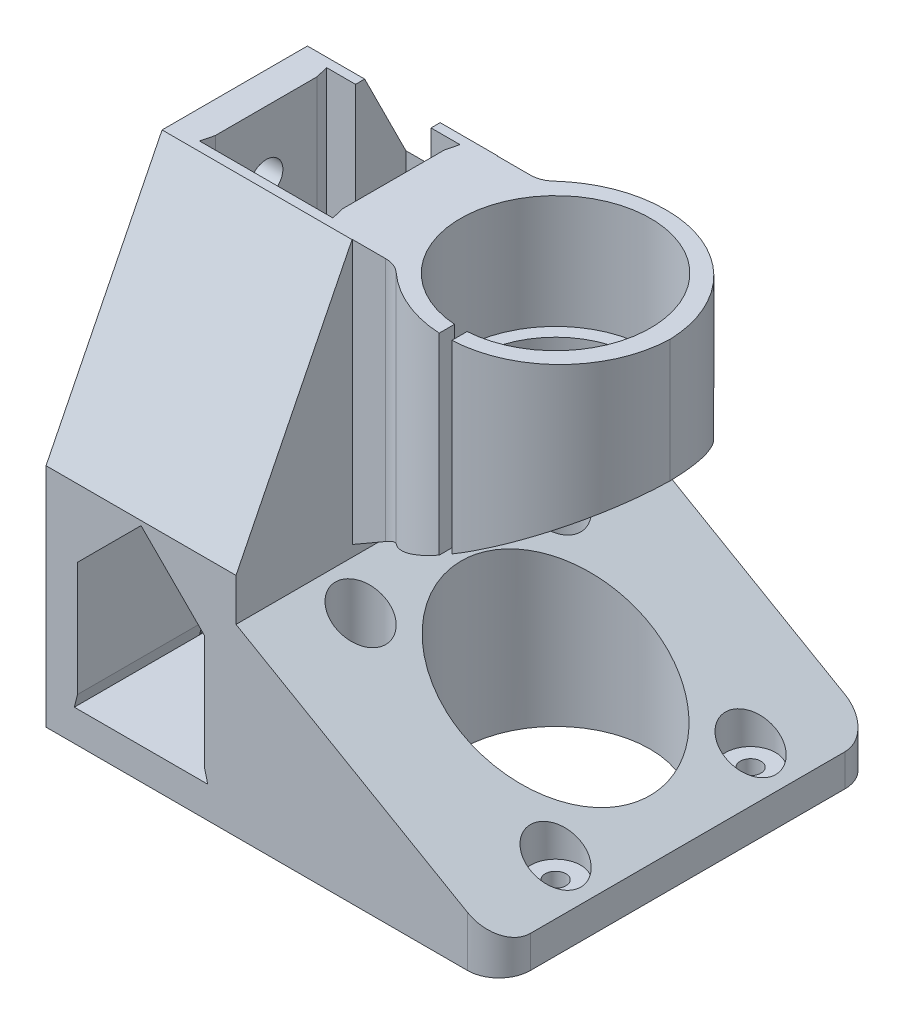
SolidWorks part; units mm, degrees
ref_plane "Front Plane" through (0, 0, 0) normal (0, 0, 1) x (1, 0, 0)
ref_plane "Top Plane" through (0, 0, 0) normal (0, 1, 0) x (1, 0, 0)
ref_plane "Right Plane" through (0, 0, 0) normal (1, 0, 0) x (0, 0, -1)
sketch "Sketch1" plane through (0, 0, 0) normal (0, 1, 0) x (1, 0, 0)
  line L1 (0, 0) -> (72, 0)
  line L2 (0, 0) -> (0, 60)
  line L3 (0, 60) -> (72, 60)
  line L4 (72, 0) -> (72, 60)
  dimension "D1" = 72
  dimension "D2" = 60
extrude "Boss-Extrude1" add sketch "Sketch1" along normal blind 5
sketch "Sketch2" plane through (0, 5, 0) normal (0, 1, 0) x (1, 0, 0)
  line L0 (0, 0) -> (72, 0) construction
  line L1 (0, 60) -> (5, 60)
  line L2 (0, 60) -> (0, 0)
  line L3 (0, 0) -> (5, 0)
  line L4 (5, 60) -> (5, 0)
  dimension "D1" = 5
extrude "Boss-Extrude2" add sketch "Sketch2" along normal blind 68
sketch "Sketch3" plane through (0, 5, 0) normal (0, 1, 0) x (1, 0, 0)
  line L0 (72, 60) -> (5, 60) construction
  line L1 (25.2, 60) -> (30.2, 60)
  line L2 (25.2, 60) -> (25.2, 0)
  line L3 (25.2, 0) -> (30.2, 0)
  line L4 (30.2, 60) -> (30.2, 0)
  line L5 (5, 0) -> (72, 0) construction
  line L6 (5, 0) -> (5, 60) construction
  dimension "D1" = 5
  dimension "D2" = 20.2
extrude "Boss-Extrude3" add sketch "Sketch3" along normal blind 68
sketch "Sketch11" plane through (0, 0, -60) normal (0, 0, -1) x (-1, 0, 0)
  line L0 (-25.2, 25.2) -> (-15.1, 35.3)
  line L1 (-25.2, 73) -> (-25.2, 5) construction
  line L2 (-15.1, 35.3) -> (-5, 25.2)
  line L3 (-5, 73) -> (-5, 5) construction
  line L4 (-5, 25.2) -> (-5, 73)
  line L5 (-5, 73) -> (-25.2, 73)
  line L6 (-25.2, 73) -> (-25.2, 25.2)
  line L7 (-25.2, 5) -> (-5, 5) construction
  dimension "D1" = 20.2
  dimension "D2" = 20.2
  dimension "D3" = 45
  dimension "D4" = 45
extrude "Boss-Extrude4" add sketch "Sketch11" against normal up to surface (60 mm away) up to face at (26.48, 31.2, 0)
chamfer "Chamfer1" distance 42 angle 30 1 edges at (30.2, 5, -30) first distance on face at (51.1, 5, -30)
sketch "Sketch12" plane through (0, 73, 0) normal (0, 1, 0) x (1, 0, 0)
  line L0 (0, 30) -> (30.2, 30) construction
  line L1 (5, 40.1) -> (25.2, 40.1)
  line L2 (5, 40.1) -> (5, 19.9)
  line L3 (5, 19.9) -> (25.2, 19.9)
  line L4 (25.2, 40.1) -> (25.2, 19.9)
  line L5 (5, 40.1) -> (25.2, 19.9) construction
  line L6 (5, 19.9) -> (25.2, 40.1) construction
  line L8 (30.2, 0) -> (30.2, 60) construction
  line L9 (0, 60) -> (0, 0) construction
  point P0 (15.1, 30)
  point P8 (15.2, 30)
  point P9 (15.1, 30)
  dimension "D1" = 20.2
  dimension "D2" = 20.2
  dimension "D3" = 5
extrude "Cut-Extrude8" cut sketch "Sketch12" against normal up to surface (68 mm away) up to face at (15.1, 5, -30)
sketch "Sketch5" plane through (0, 5, 0) normal (0, 1, 0) x (1, 0, 0)
  line L0 (72, 0) -> (72, 60) construction
  line L1 (5, 0) -> (25.2, 0) construction
  circle A0 centre (51, 30) radius 15
  dimension "D1" = 30
  dimension "D2" = 21
  dimension "D3" = 30
extrude "Cut-Extrude1" cut sketch "Sketch5" against normal through all both and the other way through all
sketch "Sketch8" plane through (5, 0, 0) normal (1, 0, 0) x (0, 0, -1)
  line L0 (0, 73) -> (60, 73) construction
  line L1 (30, 73) -> (30, 29.2487) construction
  line L2 (0, 29.2487) -> (60, 29.2487) construction
  circle A0 centre (30, 63) radius 2.65
  dimension "D1" = 5.3
  dimension "D2" = 10
extrude "Cut-Extrude5" cut sketch "Sketch8" against normal blind 10
sketch "Sketch9" plane through (0, 0, 0) normal (0, -1, 0) x (1, 0, 0)
  line L1 (0, -60) -> (0, 0) construction
  line L2 (0, -30) -> (72, -30) construction
  line L3 (72, 0) -> (72, -60) construction
  circle A0 centre (15, -30) radius 2.65
  dimension "5.3" = 5.3
  dimension "D2" = 15
extrude "Cut-Extrude6" cut sketch "Sketch9" against normal through all both and the other way through all contours A0
fillet "Fillet1" radius 5 2 edges at (72, 2.5577, -60) (72, 2.5577, 0)
sketch "Sketch10" plane through (0, 0, 0) normal (-1, 0, 0) x (0, 0, 1)
  line L0 (-60, 0) -> (0, 0) construction
  line L1 (0, 73) -> (0, 0) construction
  circle A0 centre (-30, 15) radius 2.65
  dimension "D3" = 5.3
  dimension "D1" = 15
  dimension "D2" = 30
extrude "Cut-Extrude7" cut sketch "Sketch10" against normal blind 10
sketch "Sketch13" plane through (0, 0, 0) normal (0, 0, 1) x (1, 0, 0)
  line L0 (5, 5) -> (4.5, 5)
  line L1 (4.5, 5) -> (5, 7)
  line L2 (5, 7) -> (5, 5)
  line L3 (25.2, 5) -> (25.7, 5)
  line L4 (25.7, 5) -> (25.2, 7)
  line L5 (25.2, 25.2) -> (25.2, 5) construction
  line L6 (25.2, 7) -> (25.2, 5)
  dimension "D1" = 2
  dimension "D2" = 2
  dimension "D3" = 0.5
  dimension "D4" = 0.5
extrude "Cut-Extrude9" cut sketch "Sketch13" against normal through all both and the other way through all
sketch "Sketch14" plane through (0, 73, 0) normal (0, 1, 0) x (1, 0, 0)
  line L0 (15.1, 44.9993) -> (15.1, 15.0007) construction
  line L3 (25.2, 40.1) -> (5, 40.1) construction
  line L4 (9.1, 40.1) -> (21.1, 40.1)
  line L5 (9.1, 40.1) -> (9.1, 48.1)
  line L6 (9.1, 48.1) -> (21.1, 48.1)
  line L7 (21.1, 40.1) -> (21.1, 48.1)
  line L8 (15.1, 48.1) -> (15.1, 40.1) construction
  line L14 (25.2, 19.9) -> (25.7, 19.9)
  line L15 (25.7, 19.9) -> (25.2, 21.9)
  line L16 (25.2, 19.9) -> (25.2, 40.1) construction
  line L17 (25.2, 21.9) -> (25.2, 19.9)
  line L18 (5, 19.9) -> (4.5, 19.9)
  line L19 (4.5, 19.9) -> (5, 21.9)
  line L20 (5, 40.1) -> (5, 19.9) construction
  line L21 (5, 21.9) -> (5, 19.9)
  line L22 (25.2, 40.1) -> (25.7, 40.1)
  line L23 (25.7, 40.1) -> (25.2, 38.1)
  line L24 (25.2, 38.1) -> (25.2, 40.1)
  line L25 (5, 40.1) -> (4.5, 40.1)
  line L26 (4.5, 40.1) -> (5, 38.1)
  line L27 (5, 38.1) -> (5, 40.1)
  dimension "D1" = 8
  dimension "D2" = 12
  dimension "D3" = 2
  dimension "D4" = 0.5
  dimension "D5" = 2
  dimension "D6" = 0.5
  dimension "D7" = 2
  dimension "D8" = 0.5
  dimension "D9" = 0.5
  dimension "D10" = 2
extrude "Cut-Extrude10" cut sketch "Sketch14" against normal up to surface (68 mm away) up to face at (15, 5, -32.65)
ref_plane "Bearing Base Plane" through (0, 55, 0) normal (0, 1, 0) x (1, 0, 0)
sketch "Sketch15" plane through (30.2, 0, 0) normal (1, 0, 0) x (0, 0, -1)
  line L1 (12.5, 53.5) -> (47.5, 53.5)
  line L2 (12.5, 53.5) -> (12.5, 73)
  line L3 (12.5, 73) -> (47.5, 73)
  line L4 (47.5, 53.5) -> (47.5, 73)
  line L7 (0, 73) -> (60, 73) construction
  line L8 (33, 55) -> (-33, 55) construction
  point P21 (30, 73)
  dimension "D1" = 35
  dimension "D2" = 1.5
extrude "Boss-Extrude5" add sketch "Sketch15" along normal blind 39
sketch "Sketch16" plane through (0, 55, 0) normal (0, -1, 0) x (1, 0, 0)
  circle A0 centre (51, -30) radius 15.1
  dimension "D1" = 30.2
extrude "Cut-Extrude11" cut sketch "Sketch16" against normal through all
sketch "Sketch17" plane through (0, 53.5, 0) normal (0, -1, 0) x (1, 0, 0)
  circle A0 centre (51, -30) radius 13
  dimension "D1" = 26
extrude "Cut-Extrude12" cut sketch "Sketch17" against normal through all
fillet "Fillet2" radius 18 2 edges at (69.2, 63.25, -47.5) (69.2, 63.25, -12.5)
chamfer "Chamfer2" distance 22.5 angle 60 1 edges at (30.2, 53.5, -30) first distance on face at (30.2, 57.1872, -30)
sketch "Sketch6" plane through (0, 0, 0) normal (0, -1, 0) x (1, 0, 0)
  line L1 (35.5, -14.5) -> (66.5, -14.5) construction
  line L2 (35.5, -14.5) -> (35.5, -45.5) construction
  line L3 (35.5, -45.5) -> (66.5, -45.5) construction
  line L4 (66.5, -14.5) -> (66.5, -45.5) construction
  line L5 (35.5, -14.5) -> (66.5, -45.5) construction
  line L6 (35.5, -45.5) -> (66.5, -14.5) construction
  circle A0 centre (66.5, -14.5) radius 1.65
  circle A1 centre (66.5, -45.5) radius 1.65
  circle A2 centre (35.5, -45.5) radius 1.65
  circle A3 centre (35.5, -14.5) radius 1.65
  point P0 (51, -30)
  dimension "D3" = 3.3
  dimension "D1" = 31
  dimension "D2" = 31
extrude "Cut-Extrude2" cut sketch "Sketch6" against normal through all
sketch "Sketch7" plane through (0, 5, 0) normal (0, 1, 0) x (1, 0, 0)
  circle A0 centre (66.5, 45.5) radius 4
  circle A1 centre (66.5, 14.5) radius 4
  circle A2 centre (35.5, 14.5) radius 4
  circle A4 centre (35.5, 45.5) radius 4
  dimension "D1" = 8
extrude "Cut-Extrude4" cut sketch "Sketch7" along normal through all
sketch "Sketch18" plane through (0, 73, 0) normal (0, 1, 0) x (1, 0, 0)
  line L0 (51, 52.2266) -> (51, 7.7734) construction
  line L5 (52, 22.5) -> (50, 22.5)
  line L6 (52, 22.5) -> (52, 7.5)
  line L7 (52, 7.5) -> (50, 7.5)
  line L8 (50, 22.5) -> (50, 7.5)
  line L9 (52, 22.5) -> (50, 7.5) construction
  line L10 (52, 7.5) -> (50, 22.5) construction
  line L11 (51, 22.5) -> (51, 7.5) construction
  circle A0 centre (51, 30) radius 15 construction
  point P0 (51, 15)
  point P10 (51, 30)
  dimension "D1" = 2
  dimension "D2" = 15
extrude "Cut-Extrude13" cut sketch "Sketch18" against normal blind 40
chamfer "Chamfer3" distance 37 angle 26.5 2 edges at (15.1, 73, 0) (15.1, 73, -60) first distance on face at (15.0286, 18.2714, 0) first distance on face at (15.1, 15.6714, -60)
sketch "Sketch19" plane through (0, 73, 0) normal (0, 1, 0) x (1, 0, 0)
  line L0 (30.2, 60) -> (30.2, 47.5) construction
  line L1 (30.2, 51.5) -> (35.5, 51.5)
  line L2 (30.2, 51.5) -> (30.2, 41.5)
  line L3 (30.2, 41.5) -> (35.5, 41.5)
  line L4 (35.5, 51.5) -> (35.5, 41.5)
  line L5 (30.2, 12.5) -> (30.2, 0) construction
  line L6 (30.2, 8.5) -> (35.5, 8.5)
  line L7 (30.2, 8.5) -> (30.2, 18.5)
  line L8 (30.2, 18.5) -> (35.5, 18.5)
  line L9 (35.5, 8.5) -> (35.5, 18.5)
  arc A0 (34.8542, 41.5525) -> (38.9641, 47.5) centre (35.5, 45.5) ccw construction
  circle A1 centre (35.5, 45.5) radius 4 construction
  arc A2 (38.9641, 12.5) -> (34.8542, 18.4475) centre (35.5, 14.5) ccw construction
  circle A3 centre (35.5, 14.5) radius 4 construction
  dimension "D1" = 10
  dimension "D2" = 5.3
  dimension "D3" = 5.3
  dimension "D4" = 10
extrude "Cut-Extrude14" cut sketch "Sketch19" against normal up to surface (46.8112 mm away) up to face at (39.5, 23.8794, -45.5)
fillet "Fillet3" radius 19 2 edges at (38.9641, 54.53, -47.5) (38.9641, 54.53, -12.5)
mirror "Mirror1" [suppressed] of bodies 114
delete or keep bodies "Body-Delete/Keep 1" [suppressed] type delete bodies bodies 114
